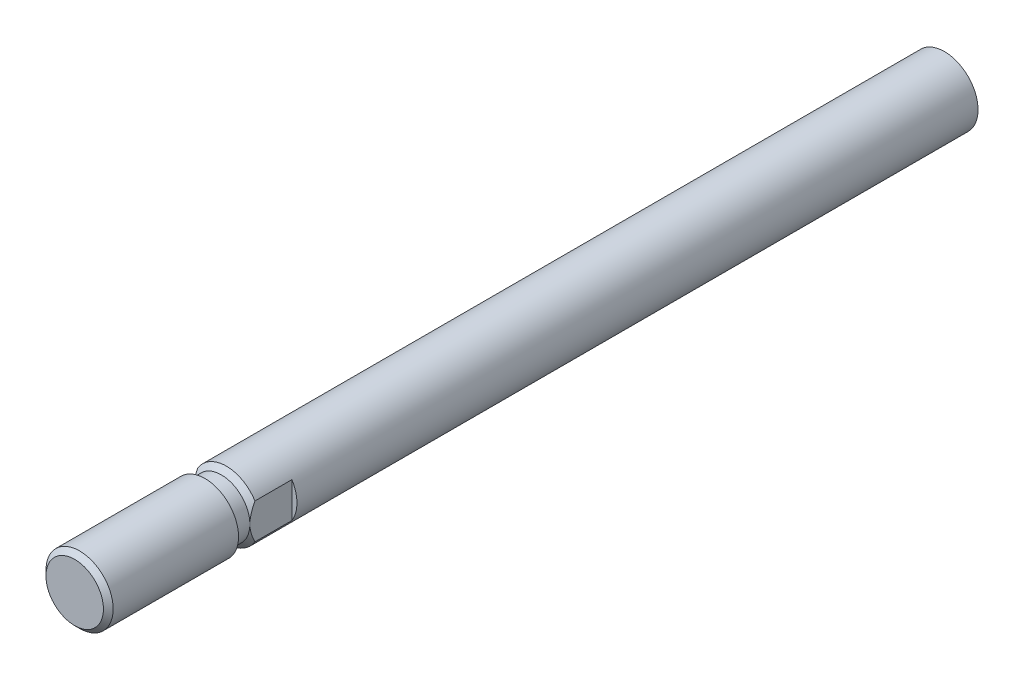
SolidWorks part; units mm, degrees
ref_plane "前视基准面" through (0, 0, 0) normal (0, 0, 1) x (1, 0, 0)
ref_plane "上视基准面" through (0, 0, 0) normal (0, 1, 0) x (1, 0, 0)
ref_plane "右视基准面" through (0, 0, 0) normal (1, 0, 0) x (0, 0, -1)
sketch "草图1" plane through (0, 0, 0) normal (1, 0, 0) x (0, 0, -1)
  line L0 (-38.5, 0) -> (38.5, 0) construction
  line L1 (0, 0) -> (0, 12.5) construction
  line L2 (0, 12.5) -> (15, 12.5) construction
  line L3 (15, 12.5) -> (77, 12.5) construction
  line L4 (51.5, 10) -> (51.5, -10) construction
  line L5 (-38.5, 0) -> (-52.5, 0) construction
  line L6 (-52.5, 10) -> (-52.5, -10) construction
  line L7 (-52.5, 0) -> (-79.5, 0) construction
  line L8 (38.5, 0) -> (59.5, 0) construction
  line L9 (59.5, 10) -> (59.5, -10) construction
  line L10 (-79.5, 4) -> (-79.5, -4) construction
  circle A0 centre (-31, 0) radius 4.864
  circle A1 centre (50.5, 0) radius 4
  point P6 (-24, 0)
  point P8 (24, 0)
  point P9 (-31, 0)
  point P10 (31, 0)
  point P13 (51.5, 0)
  point P16 (-49.7, 0)
  point P18 (-41.7, 0)
  point P21 (-52.5, 4)
  point P22 (-64, 0)
  point P24 (-62.05, 0)
  point P25 (-57.05, 0)
  point P26 (-74.85, 0)
  point P27 (-69.85, 0)
  point P28 (50.5, 0)
  dimension "D2" = 2.8
  dimension "X" = 9.728
  dimension "P1" = 8
  dimension "D1" = 77
  dimension "行程" = 15
  dimension "A" = 62
  dimension "S" = 25
  dimension "F" = 14.5
  dimension "G1" = 7.5
  dimension "D1用" = 13
  dimension "L" = 20
  dimension "B" = 14
  dimension "M" = 8
  dimension "D3" = 1.95
  dimension "V" = 8
  dimension "C" = 27
  dimension "H" = 15.5
  dimension "D4" = 4.65
  dimension "E" = 5
  dimension "J" = 5
  dimension "D" = 21
  dimension "G" = 12
  dimension "L1" = 20
  dimension "K" = 8
sketch "草图2" plane through (0, 0, 0) normal (0, 0, 1) x (1, 0, 0)
  line L0 (-6, 0) -> (6, 0) construction
  line L1 (0, 15.0111) -> (-13, 7.5056)
  line L2 (-13, 7.5056) -> (-13, -7.5056)
  line L3 (-13, -7.5056) -> (0, -15.0111)
  line L4 (0, -15.0111) -> (13, -7.5056)
  line L5 (13, -7.5056) -> (13, 7.5056)
  line L6 (13, 7.5056) -> (0, 15.0111)
  line L7 (0, 7.5056) -> (-6.5, 3.7528)
  line L8 (-6.5, 3.7528) -> (-6.5, -3.7528)
  line L9 (-6.5, -3.7528) -> (0, -7.5056)
  line L10 (0, -7.5056) -> (6.5, -3.7528)
  line L11 (6.5, -3.7528) -> (6.5, 3.7528)
  line L12 (6.5, 3.7528) -> (0, 7.5056)
  line L13 (0, 0) -> (0, 4) construction
  circle A0 centre (0, 0) radius 13 construction
  circle A1 centre (0, 0) radius 6.5 construction
  circle A2 centre (0, 0) radius 14.5 construction
  dimension "T1" = 26
  dimension "T" = 13
  dimension "P" = 29
  dimension "Q" = 12
sketch "行程" plane through (0, 0, 0) normal (1, 0, 0) x (0, 0, -1)
  line L0 (24, 0) -> (9, 0)
  line L1 (-38.5, 0) -> (38.5, 0) construction
  dimension "D1" = 15
sketch "草图4" plane through (0, 0, 0) normal (0, 0, 1) x (1, 0, 0)
  circle A0 centre (0, 0) radius 4
extrude "凸台-拉伸1" add sketch "草图4" against normal up to vertex (-64 mm away) from vertex up to point (0, 0, 64) starting at point (0, 0, 79.5)
cosmetic thread "装饰螺纹线1" parameters "D2"=6.8
cosmetic thread "装饰螺纹线2" parameters "D2"=6.8
sketch "草图5" plane through (0, 0, 64) normal (0, 0, -1) x (-1, 0, 0)
  circle A0 centre (0, 0) radius 3.4
  dimension "D1" = 6.8
extrude "凸台-拉伸2" add sketch "草图5" along normal up to vertex (1.95 mm away) up to point (0, 0, 62.05)
sketch "草图6" plane through (0, 0, 62.05) normal (0, 0, -1) x (-1, 0, 0)
  circle A0 centre (0, 0) radius 4
extrude "凸台-拉伸3" add sketch "草图6" along normal up to vertex (86.05 mm away) up to point (0, 0, -24)
sketch "草图7" plane through (0, 0, 0) normal (0, 0, 1) x (1, 0, 0)
  line L0 (6.5, -3.7528) -> (6.5, 3.7528) construction
  line L1 (6.5, 3.7528) -> (0, 7.5056) construction
  line L2 (0, 7.5056) -> (-6.5, 3.7528) construction
  line L3 (-6.5, 3.7528) -> (-6.5, -3.7528) construction
  line L4 (-6.5, -3.7528) -> (0, -7.5056) construction
  line L5 (0, -7.5056) -> (6.5, -3.7528) construction
  line L6 (6.5, -3.7528) -> (6.5, 3.7528)
  line L7 (6.5, 3.7528) -> (0, 7.5056)
  line L8 (0, 7.5056) -> (-6.5, 3.7528)
  line L9 (-6.5, 3.7528) -> (-6.5, -3.7528)
  line L10 (-6.5, -3.7528) -> (0, -7.5056)
  line L11 (0, -7.5056) -> (6.5, -3.7528)
chamfer "倒角1" distance 0.58 angle 45 1 edges at (4, 0, 79.5)
chamfer "倒角2" distance 0.6 angle 45 1 edges at (-4, 0, 62.05)
sketch "草图9" plane through (0, 0, 0) normal (0, 0, 1) x (1, 0, 0)
  line L0 (-3.4, 7.5056) -> (-3.4, -7.5056)
  line L1 (3.4, 7.5056) -> (3.4, -7.5056)
  line L2 (-3.4, 7.5056) -> (3.4, 7.5056)
  line L3 (-3.4, -7.5056) -> (3.4, -7.5056)
  circle A0 centre (0, 0) radius 3.4 construction
extrude "切除-拉伸1" cut sketch "草图9" along normal up to vertex (62.05 mm away) from vertex flip side to cut up to point (0, 0, 62.05) starting at point (0, 0, 57.05)
